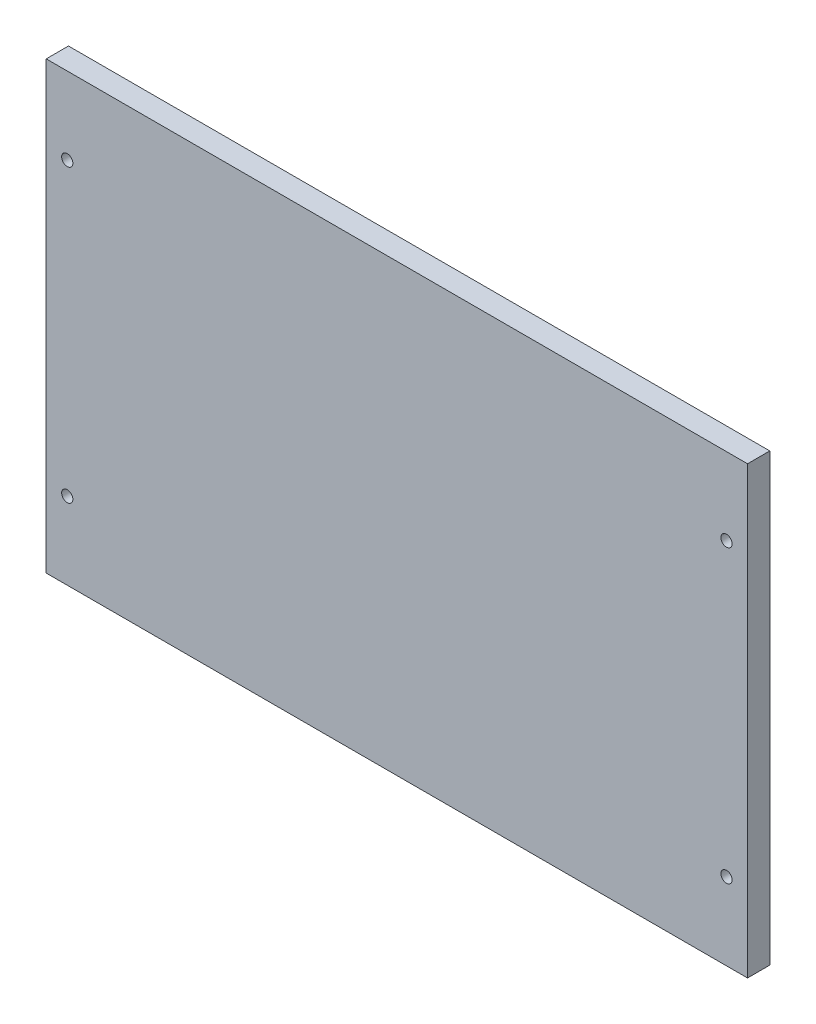
SolidWorks part; units mm, degrees
ref_plane "Front Plane" through (0, 0, 0) normal (0, 0, 1) x (1, 0, 0)
ref_plane "Top Plane" through (0, 0, 0) normal (0, 1, 0) x (1, 0, 0)
ref_plane "Right Plane" through (0, 0, 0) normal (1, 0, 0) x (0, 0, -1)
sketch "Sketch1" plane through (0, 0, 0) normal (0, 0, 1) x (1, 0, 0)
  line L0 (100, 127) -> (100, 0) construction
  line L1 (0, 0) -> (200, 0)
  line L2 (0, 0) -> (0, 127)
  line L3 (0, 127) -> (200, 127)
  line L4 (200, 0) -> (200, 127)
  line L5 (0, 63.5) -> (200, 63.5) construction
  circle A3 centre (6, 105) radius 1.6
  circle A7 centre (194, 105) radius 1.6
  circle A8 centre (194, 22) radius 1.6
  circle A9 centre (6, 22) radius 1.6
  dimension "D11" = 3.2
  dimension "D1" = 127
  dimension "D2" = 200
  dimension "D12" = 6
  dimension "D13" = 22
extrude "Wall" add sketch "Sketch1" along normal blind 6.35
sketch "Sketch2" [suppressed] plane through (0, 0, 6.35) normal (0, 0, 1) x (1, 0, 0)
  line L0 (135.35, 127) -> (135.35, 98.425) construction
  line L1 (270.7, 127) -> (0, 127) construction
  line L2 (135.35, 98.425) -> (66.6667, 98.425) construction
  line L3 (135.35, 98.425) -> (204.0333, 98.425) construction
  line L4 (0, 127) -> (0, 0) construction
  circle A0 centre (135.35, 98.425) radius 3.9687
  circle A1 centre (66.6667, 98.425) radius 3.9688
  circle A2 centre (204.0333, 98.425) radius 3.9687
  dimension "D2" = 7.9375
  dimension "D1" = 28.575
  dimension "D3" = 66.6667
extrude "RodSupportCutouts" [suppressed] cut sketch "Sketch2" against normal up to next
sketch "Sketch3" [suppressed] plane through (0, 0, 6.35) normal (0, 0, 1) x (1, 0, 0)
  line L1 (25.4, 88.9) -> (245.3, 88.9)
  line L2 (25.4, 88.9) -> (25.4, 114.3)
  line L3 (25.4, 114.3) -> (245.3, 114.3)
  line L4 (245.3, 88.9) -> (245.3, 114.3)
  line L5 (25.4, 88.9) -> (245.3, 114.3) construction
  line L6 (25.4, 114.3) -> (245.3, 88.9) construction
  line L7 (270.7, 127) -> (0, 127) construction
  line L8 (0, 127) -> (0, 0) construction
  point P0 (135.35, 101.6)
  point P9 (135.35, 127)
  dimension "D1" = 25.4
  dimension "D2" = 25.4
  dimension "D3" = 25.4
extrude "CannulaLargeCutout" [suppressed] cut sketch "Sketch3" against normal up to next
sketch "Sketch4" [suppressed] plane through (0, 0, 9.525) normal (0, 0, 1) x (1, 0, 0)
  line L0 (6, 103.5) -> (194, 103.5) construction
  line L1 (6, 105) -> (6, 22) construction
  line L2 (194, 105) -> (194, 22) construction
  line L3 (200, 127) -> (0, 127) construction
  line L4 (0, 127) -> (0, 0) construction
  circle A0 centre (60, 103.5) radius 6.35
  circle A1 centre (20, 103.5) radius 6.35
  circle A2 centre (100, 103.5) radius 6.35
  circle A3 centre (140, 103.5) radius 6.35
  circle A4 centre (60, 63.5) radius 6.35
  circle A5 centre (100, 63.5) radius 6.35
  circle A6 centre (140, 63.5) radius 6.35
  circle A7 centre (60, 23.5) radius 6.35
  circle A8 centre (100, 23.5) radius 6.35
  circle A9 centre (140, 23.5) radius 6.35
  circle A10 centre (20, 63.5) radius 6.35
  circle A11 centre (20, 23.5) radius 6.35
  circle A12 centre (180, 103.5) radius 6.35
  circle A13 centre (180, 63.5) radius 6.35
  circle A14 centre (180, 23.5) radius 6.35
  point P42 (100, 127)
  point P45 (0, 63.5)
  dimension "D3" = 12.7
  dimension "D1" = 5
  dimension "D2" = 3
extrude "CannulaHoles" [suppressed] cut sketch "Sketch4" against normal up to next
ref_plane "LeftBoundary" [suppressed] through (25.4, 0, 0) normal (-1, 0, 0) x (0, 0, 1)
ref_plane "RightBoundary" [suppressed] through (245.3, 0, 0) normal (1, 0, 0) x (0, 0, -1)
ref_plane "TopBoundary" [suppressed] through (0, 101.6, 0) normal (0, 1, 0) x (1, 0, 0)
ref_plane "BottomBoundary" [suppressed] through (0, 25.4, 0) normal (0, -1, 0) x (-1, 0, 0)
sketch "Sketch5" [suppressed] plane through (0, 0, 6.35) normal (0, 0, 1) x (1, 0, 0)
  line L4 (25.4, 3.4925) -> (25.4, -3.4925) construction
  line L5 (3.4925, 101.6) -> (-3.4925, 101.6) construction
  circle A0 centre (25.4, 101.6) radius 3.9687
  dimension "D1" = 7.9375
extrude "RodSupportCutout" [suppressed] cut sketch "Sketch5" along normal blind 3.35 from surface
pattern_linear "SupportPattern" [suppressed] count 7 spacing 36.65 count 5 spacing 19.05 of bodies 105
sketch "Sketch6" [suppressed] plane through (0, 0, 6.35) normal (0, 0, 1) x (1, 0, 0)
  line L0 (47, 122) -> (50.2, 122)
  line L1 (149.8, 122) -> (153, 122)
  line L2 (149.8, 122) -> (149.8, 5)
  line L3 (149.8, 5) -> (153, 5)
  line L4 (153, 122) -> (153, 5)
  line L5 (47, 122) -> (47, 5)
  line L6 (47, 5) -> (50.2, 5)
  line L7 (50.2, 122) -> (50.2, 5)
  line L8 (0, 127) -> (0, 0) construction
  line L9 (0, 0) -> (200, 0) construction
  line L10 (200, 0) -> (200, 127) construction
  line L11 (0, 0) -> (200, 0) construction
  point P7 (200, 57)
  dimension "D1" = 117
  dimension "D2" = 5
  dimension "SlitDiameter" = 3.2
  dimension "D4" = 47
  dimension "D5" = 47
  dimension "D6" = 5
  dimension "D7" = 117
  dimension "D3" = 3.2
extrude "Cut-Extrude1" [suppressed] cut sketch "Sketch6" against normal through all
equation "\"Length\"= 283mm"
equation "\"Width\"= 225mm"
equation "\"WallThickness\"= 0.25in"
equation "\"UpperWaterJacketThickness\"= 28mm"
equation "\"SpacerHeight\"= 80.2mm"
equation "\"SpacerCornerWidth\"= 10mm"
equation "\"SpacerCornerHeight\"= 60.16mm"
equation "\"SpacerPegDiameter\"= 10mm"
equation "\"SpacerPegHeight\"= 10mm"
equation "\"TubingShort\"= 110mm"
equation "\"TubingLong\"= 175mm"
equation "\"PlateLength\"= 252mm"
equation "\"PlateWidth\"= 190mm"
equation "\"PlateHoleDiameter\"= 5.9mm"
equation "\"PlateHoleBottom\"= 2mm"
equation "\"PlateHoleSide\"= 1.55mm"
equation "\"PlateHoleSpacing\"= 3.1mm"
equation "\"PlateThickness\"= 1.55mm"
equation "\"ReservoirBottom\"= 12.5mm"
equation "\"ReservoirSupportWidth\"= 12mm"
equation "\"ReservoirSupportHeight\"= 15.1mm"
equation "\"ReservoirSupportPlacementHeight\"= 50mm"
equation "\"ReservoirHoleDiameter\"= 12.7mm"
equation "\"ReservoirHoleRight\"= 25mm"
equation "\"ReservoirHoleTop\"= \"ReservoirSupportPlacementHeight\""
equation "\"ReservoirHeight\"= 90mm"
equation "\"ReservoirPortBottom\"= 4mm"
equation "\"ReservoirPortTop\"= 10mm"
equation "\"ReservoirPortWidth\"= 101mm"
equation "\"CustomSpacerHeight\"= 5in"
equation "\"CustomSpacerRodHoleHeight\"= .75in"
equation "\"CustomSpacerRodHoleDiameter\"= .3125in"
equation "\"ScrewBlockSide\"= 12mm"
equation "\"ScrewBlockUpperHeight\"= 16mm"
equation "\"ScrewBlockLowerHeight\"= 16mm"
equation "\"InternalLength\"= 258mm"
equation "\"InternalWidth\"= 200mm"
equation "\"CustomSpacerPegHeight\"= 1in"
equation "\"CustomSpacerScrewBore\"=3.2mm"
equation "\"CustomSpacerScrewDepth\"=10mm"
equation "\"D1@Sketch1\"=\"CustomSpacerHeight\""
equation "\"D2@Sketch1\"=\"WallLength\""
equation "\"D11@Sketch1\"=\"CustomSpacerScrewBore\""
equation "\"D12@Sketch1\"   = \"ScrewBlockSide\"/2"
equation "\"D13@Sketch1\"=\"ScrewBlockUpperHeight\"+\"ScrewBlockSide\"/2"
equation "\"D1@Wall\" = \"WallThickness\""
equation "\"D1@Sketch2\"=\"CustomSpacerRodHoleHeight\" + \"CustomSpacerRodHoleDiameter\" +0.0625in"
equation "\"D2@Sketch2\"=\"CustomSpacerRodHoleDiameter\""
equation "\"D3@Sketch2\"=\"InternalWidth\" / 3"
equation "\"D1@Sketch3\"=1in"
equation "\"WallLength\"= \"InternalWidth\""
equation "\"D1@Sketch5\"=\"CustomSpacerRodHoleDiameter\""
equation "\"D1@RodSupportCutout\"      = \"WallThickness\" - 3"
equation "\"SlitDiameter@Sketch6\" = \"CustomSpacerScrewBore\""
equation "\"D3@Sketch6\"=\"CustomSpacerScrewBore\""
